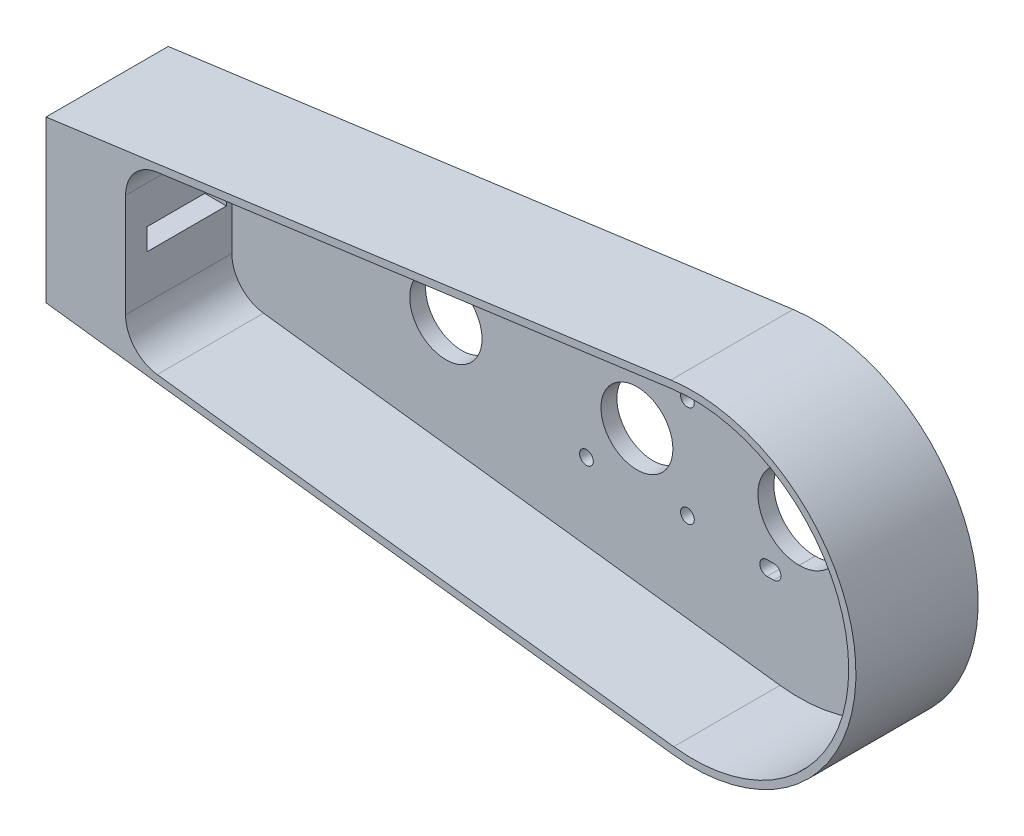
SolidWorks part; units mm, degrees
ref_plane "Plano frontal" through (0, 0, 0) normal (0, 0, 1) x (1, 0, 0)
ref_plane "Plano superior" through (0, 0, 0) normal (0, 1, 0) x (1, 0, 0)
ref_plane "Plano direito" through (0, 0, 0) normal (1, 0, 0) x (0, 0, -1)
sketch "Esboço1" plane through (0, 0, 0) normal (0, 0, 1) x (1, 0, 0)
  line L0 (-54.8291, -0.9911) -> (-176.9291, -0.9911) construction
  line L1 (-54.8291, -0.9911) -> (-23.2291, -0.9911) construction
  line L2 (-0.025, 0) -> (0.025, 0) construction
  line L3 (-0.025, 11.375) -> (0.025, 11.375)
  line L4 (-0.025, -11.375) -> (0.025, -11.375)
  line L5 (22.1604, 14.4589) -> (24.0104, 14.4589) construction
  line L6 (22.1604, 16.4589) -> (24.0104, 16.4589)
  line L7 (22.1604, 12.4589) -> (24.0104, 12.4589)
  line L8 (-8.8896, 14.4589) -> (-7.0396, 14.4589) construction
  line L9 (-8.8896, 16.4589) -> (-7.0396, 16.4589)
  line L10 (-8.8896, 12.4589) -> (-7.0396, 12.4589)
  line L11 (22.1604, -16.4411) -> (24.0104, -16.4411) construction
  line L12 (22.1604, -18.4411) -> (24.0104, -18.4411)
  line L13 (22.1604, -14.4411) -> (24.0104, -14.4411)
  line L14 (-8.8896, -16.4411) -> (-7.0396, -16.4411) construction
  line L15 (-8.8896, -18.4411) -> (-7.0396, -18.4411)
  line L16 (-8.8896, -14.4411) -> (-7.0396, -14.4411)
  line L17 (20.1604, -16.4411) -> (26.0104, -16.4411) construction
  line L18 (-176.9291, 19.5089) -> (-5.7899, 42.7093)
  line L19 (-176.9291, -21.4911) -> (-5.3037, -42.7724)
  line L20 (-11.4, 0) -> (11.4, 0) construction
  line L21 (43.1, 0) -> (43.1, 10.583) construction
  line L22 (25.6606, -17.5711) -> (35.5618, -24.351) construction
  line L23 (25.6606, -17.5711) -> (28.9641, -12.7467) construction
  line L24 (37.9405, -20.8771) -> (35.5618, -24.351) construction
  line L25 (-4.4888, -10.4625) -> (0.0336, -12.392) construction
  line L26 (-4.4888, -10.4625) -> (-6.2548, -14.6016) construction
  line L27 (-6.2548, -14.6016) -> (-2.0762, -16.3844) construction
  line L28 (-176.9291, 19.5089) -> (-176.9291, -21.4911)
  line L29 (-44.8791, 18.7589) -> (-44.8791, -0.9911) construction
  line L30 (-44.8791, -0.9911) -> (-30.9138, 12.9742) construction
  line L31 (-44.8791, -0.9911) -> (-58.8445, -14.9565) construction
  line L32 (-156.9291, 22.2202) -> (-156.9291, -23.9711)
  circle A1 centre (-44.8791, -0.9911) radius 9.95
  circle A2 centre (-44.8791, -0.9911) radius 19.75 construction
  circle A3 centre (-44.8791, 18.7589) radius 1.9 construction
  circle A4 centre (-25.1291, -0.9911) radius 1.9 construction
  circle A5 centre (-44.8791, -20.7411) radius 1.9 construction
  circle A6 centre (-64.6291, -0.9911) radius 1.9 construction
  circle A7 centre (0, 0) radius 43.1
  arc A8 (-0.025, 11.375) -> (-0.025, -11.375) centre (-0.025, 0) ccw
  arc A9 (0.025, -11.375) -> (0.025, 11.375) centre (0.025, 0) ccw
  arc A10 (22.1604, 16.4589) -> (22.1604, 12.4589) centre (22.1604, 14.4589) ccw
  arc A11 (24.0104, 12.4589) -> (24.0104, 16.4589) centre (24.0104, 14.4589) ccw
  arc A12 (-8.8896, 16.4589) -> (-8.8896, 12.4589) centre (-8.8896, 14.4589) ccw
  arc A13 (-7.0396, 12.4589) -> (-7.0396, 16.4589) centre (-7.0396, 14.4589) ccw
  arc A14 (22.1604, -18.4411) -> (22.1604, -14.4411) centre (22.1604, -16.4411) cw
  arc A15 (24.0104, -14.4411) -> (24.0104, -18.4411) centre (24.0104, -16.4411) cw
  arc A16 (-8.8896, -18.4411) -> (-8.8896, -14.4411) centre (-8.8896, -16.4411) cw
  arc A17 (-7.0396, -14.4411) -> (-7.0396, -18.4411) centre (-7.0396, -16.4411) cw
  circle A18 centre (-30.9138, 12.9742) radius 1.9
  circle A19 centre (-58.8445, -14.9565) radius 1.9
  circle A20 centre (-30.9138, -14.9565) radius 1.9
  circle A21 centre (-58.8445, 12.9742) radius 1.9
  circle A22 centre (-97.7291, -0.9911) radius 10
  circle A23 centre (4, 24) radius 2.9
  point P17 (0, 0)
  point P24 (23.0854, 14.4589)
  point P33 (-7.9646, 14.4589)
  point P40 (23.0854, -16.4411)
  point P47 (-7.9646, -16.4411)
  point P57 (-10.8896, -16.4411)
  point P61 (-34.9291, -0.9911)
  point P80 (-107.7291, -0.9911)
  point P86 (-176.9291, -0.9911)
  dimension "D1" = 19.9
  dimension "D2" = 3.8
  dimension "D16" = 20
  dimension "D19" = 5.8
  dimension "D3" = 31.6
  dimension "D4" = 4
  dimension "D5" = 34.9
  dimension "D6" = 5.85
  dimension "D7" = 36.9
  dimension "D8" = 22.75
  dimension "D9" = 22.8
  dimension "D10" = 23.55
  dimension "D11" = 31.7
  dimension "D12" = 12
  dimension "D13" = 4.5
  dimension "D14" = 45
  dimension "D15" = 72.8
  dimension "D17" = 41
  dimension "D18" = 69.2
  dimension "D20" = 24
  dimension "D21" = 4
  dimension "D22" = 20
extrude "Ressalto-extrusão1" add sketch "Esboço1" along normal blind 30.8 contours L32 L18 L28 L19 | A7 A20 A18 L18 L32 L19 A22 A1 A19 A21 | A7 A20 A18 A23 A13 L10 A12 L9 A11 L7 A10 L6 A9 L4 A8 L3 L13 A15 L12 A14 L16 A17 L15 A16 region at (-166.7307, -0.9322, 0) region at (-81.1257, 30.7399, 0) region at (27.5575, 31.5454, 0)
extrude "Ressalto-extrusão2" add sketch "Esboço1<3>" against normal blind 3 contours A7 A20 A18 A23 A13 L10 A12 L9 A11 L7 A10 L6 A9 L4 A8 L3 L13 A15 L12 A14 L16 A17 L15 A16 | A7 A20 A18 L18 L32 L19 A22 A1 A19 A21 | L32 L18 L28 L19 region at (-166.7307, -0.9322, 0) region at (-81.1257, 30.7399, 0) region at (27.5575, 31.5454, 0)
sketch "Esboço1<3>" plane through (0, 0, 0) normal (0, 0, 1) x (1, 0, 0) same geometry as "Esboço1"
sketch "Esboço4" plane through (0, 0, -3) normal (0, 0, -1) x (-1, 0, 0)
  line L6 (5.5498, -44.7572) -> (178.9291, -23.2585)
  line L7 (178.9291, -23.2585) -> (178.9291, 21.256)
  line L8 (178.9291, 21.256) -> (6.0586, 44.6912)
  line L9 (5.5498, -44.7572) -> (178.9291, -23.2585)
  line L10 (178.9291, -23.2585) -> (178.9291, 21.256)
  line L11 (178.9291, 21.256) -> (6.0586, 44.6912)
  arc A2 (6.0586, 44.6912) -> (5.5498, -44.7572) centre (0, 0) ccw
  arc A3 (6.0586, 44.6912) -> (5.5498, -44.7572) centre (0, 0) ccw
  dimension "D1" = 2
extrude "Ressalto-extrusão4" add sketch "Esboço4" against normal through all contours A3 L9 L10 L11
sketch "Esboço2" plane through (0, 0, 30.8) normal (0, 0, 1) x (1, 0, 0)
  line L6 (-5.7899, 42.7093) -> (-176.9291, 19.5089)
  line L13 (-5.7899, 42.7093) -> (-176.9291, 19.5089)
  line L16 (-176.9291, 19.5089) -> (-176.9291, -21.4911)
  line L18 (-176.9291, 19.5089) -> (-176.9291, -21.4911)
  line L19 (-176.9291, -21.4911) -> (-5.3037, -42.7724)
  line L20 (-176.9291, -21.4911) -> (-5.3037, -42.7724)
  arc A2 (-5.3037, -42.7724) -> (-5.7899, 42.7093) centre (0, 0) ccw
  arc A6 (-5.3037, -42.7724) -> (-5.7899, 42.7093) centre (0, 0) ccw
  dimension "D1" = 2
extrude "Corte-extrusão1" cut sketch "Esboço2" against normal blind 29.4
extrude "Corte-extrusão2" cut sketch "Esboço1<4>" against normal through all and the other way through all contours A22 | A1 A7 | A7 A1 | A21 | A18 | A19 | A20 | L4 A9 L3 A8 | A17 L16 A16 L15 | A15 L13 A14 L12 | A23 | L10 A13 L9 A12 | L7 A11 L6 A10 region at (0, 0, 0) region at (23.0854, 14.4589, 0) region at (-7.9646, 14.4589, 0) region at (23.0854, -16.4411, 0) region at (-7.9646, -16.4411, 0) region at (-47.9606, -1.0592, 0) region at (-39.4822, -0.8719, 0) region at (-30.9138, 12.9742, 0) region at (-58.8445, -14.9565, 0) region at (-30.9138, -14.9565, 0) region at (-58.8445, 12.9742, 0) region at (-97.7291, -0.9911, 0) region at (4, 24, 0)
sketch "Esboço1<4>" plane through (0, 0, 0) normal (0, 0, 1) x (1, 0, 0) same geometry as "Esboço1"
extrude "Ressalto-extrusão5" add sketch "Esboço1<5>" along normal through all contours L32 L18 L28 L19 region at (-166.7307, -0.9322, 0)
sketch "Esboço1<5>" plane through (0, 0, 0) normal (0, 0, 1) x (1, 0, 0) same geometry as "Esboço1"
fillet "Filete1" radius 10 2 edges at (-156.9291, 22.2202, 16.1) (-156.9291, -23.9711, 16.1)
sketch "Esboço5" plane through (-178.9291, 0, 0) normal (-1, 0, 0) x (0, 0, 1)
  line L0 (13.9, 21.256) -> (13.9, 3) construction
  line L1 (2.9, -3) -> (24.9, -3)
  line L2 (2.9, -3) -> (2.9, 3)
  line L3 (2.9, 3) -> (24.9, 3)
  line L4 (24.9, -3) -> (24.9, 3)
  line L5 (30.8, 21.256) -> (-3, 21.256) construction
  line L6 (0, 0) -> (2.9, 0) construction
  dimension "D1" = 6
  dimension "D2" = 22
extrude "Corte-extrusão3" cut sketch "Esboço5" against normal up to next
